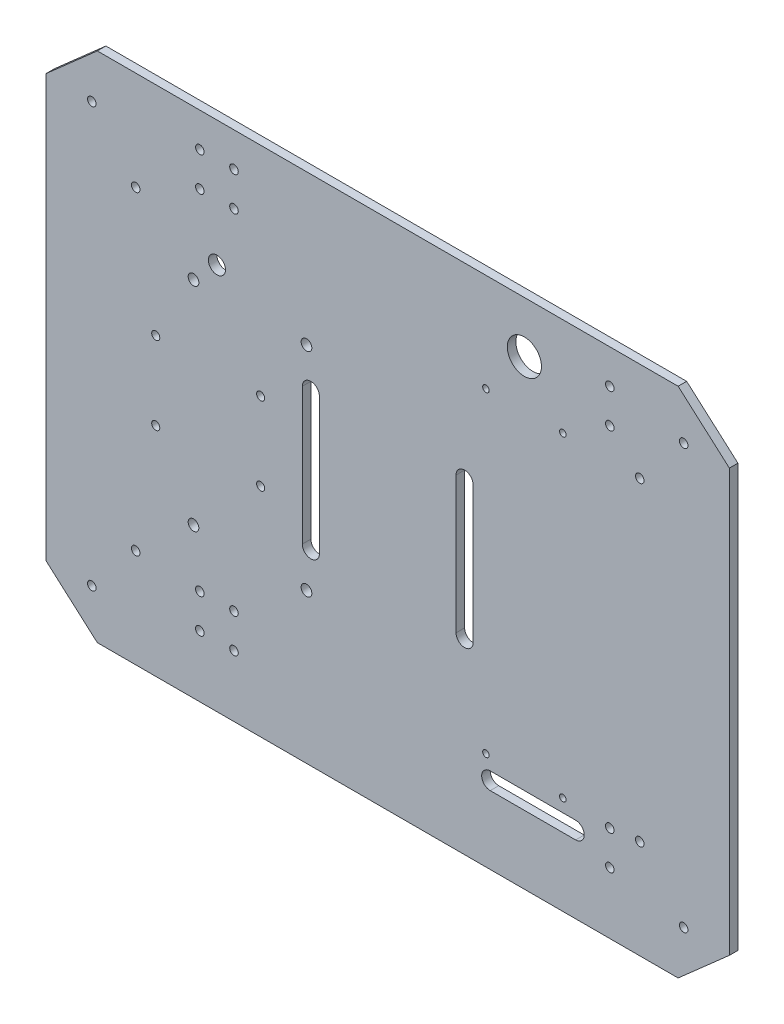
SolidWorks part; units mm, degrees
material "Thornel Mat VMA"
ref_plane "Front Plane" through (0, 0, 0) normal (0, 0, 1) x (1, 0, 0)
ref_plane "Top Plane" through (0, 0, 0) normal (0, 1, 0) x (1, 0, 0)
ref_plane "Right Plane" through (0, 0, 0) normal (1, 0, 0) x (0, 0, -1)
sketch "Sketch1" plane through (0, 0, 0) normal (0, 0, 1) x (1, 0, 0)
  line L0 (-127, 0) -> (127, 0) construction
  line L1 (0, -95.25) -> (0, 95.25) construction
  line L2 (-107.95, 0) -> (-107.95, 40.5993) construction
  line L3 (-107.95, 40.5993) -> (-95.25, 40.5993) construction
  line L4 (-95.25, 40.5993) -> (-75.7925, 56.9261) construction
  line L5 (-75.7925, 56.9261) -> (-75.7925, 76.2) construction
  line L6 (-75.7925, 76.2) -> (0, 76.2) construction
  line L7 (-95.25, 40.5993) -> (-127, 78.4375) construction
  line L8 (-75.7925, 56.9261) -> (-107.95, 95.25) construction
  line L24 (127, -78.4375) -> (127, 78.4375)
  line L25 (127, 78.4375) -> (107.95, 95.25)
  line L26 (107.95, 95.25) -> (-107.95, 95.25)
  line L27 (-107.95, 95.25) -> (-127, 78.4375)
  line L28 (-127, 78.4375) -> (-127, -78.4375)
  line L29 (-127, -78.4375) -> (-107.95, -95.25)
  line L30 (-107.95, -95.25) -> (107.95, -95.25)
  line L31 (107.95, -95.25) -> (127, -78.4375)
  point P12 (0, 0)
  dimension "D1" = 190.5
  dimension "D2" = 254
  dimension "D3" = 19.05
  dimension "D4" = 19.05
  dimension "D5" = 12.7
  dimension "D6" = 25.4
  dimension "D7" = 40
extrude "Boss-Extrude1" add sketch "Sketch1" along normal blind 3.175
sketch "Sketch2" plane through (0, 0, 3.175) normal (0, 0, 1) x (1, 0, 0)
  line L0 (-127, 0) -> (127, 0) construction
  line L1 (-127, 78.4375) -> (-127, -78.4375) construction
  line L2 (127, -78.4375) -> (127, 78.4375) construction
  line L3 (50.8, 65.0875) -> (50.8, -65.0875) construction
  line L4 (31.75, 65.0875) -> (69.85, 65.0875)
  line L5 (31.75, 65.0875) -> (31.75, -65.0875)
  line L6 (31.75, -65.0875) -> (69.85, -65.0875)
  line L7 (69.85, 65.0875) -> (69.85, -65.0875)
  line L8 (31.75, 65.0875) -> (69.85, -65.0875) construction
  line L9 (31.75, -65.0875) -> (69.85, 65.0875) construction
  line L10 (50.8, 58.7375) -> (41.275, 58.7375) construction
  line L11 (41.275, 58.7375) -> (31.75, 58.7375) construction
  circle A0 centre (36.5125, 58.7375) radius 1.2136
  circle A1 centre (36.5125, -58.7375) radius 1.2136
  circle A2 centre (65.0875, -58.7375) radius 1.2136
  circle A3 centre (65.0875, 58.7375) radius 1.2136
  point P6 (50.8, 0)
  point P17 (36.5125, 58.7375)
  dimension "D1" = 38.1
  dimension "D2" = 130.175
  dimension "D3" = 6.35
  dimension "D4" = 9.525
  dimension "D5" = 76.2
extrude "Cut-Extrude1" cut sketch "Sketch2" against normal through all contours A1 | A2 | A3 | A0 region at (36.5125, 58.7375, 3.175) region at (36.5125, -58.7375, 3.175) region at (65.0875, -58.7375, 3.175) region at (65.0875, 58.7375, 3.175)
sketch "Sketch3" plane through (0, 0, 3.175) normal (0, 0, 1) x (1, 0, 0)
  line L0 (0, 95.25) -> (0, -95.25) construction
  line L1 (107.95, 95.25) -> (-107.95, 95.25) construction
  line L2 (-107.95, -95.25) -> (107.95, -95.25) construction
  line L3 (127, 0) -> (-127, 0) construction
  line L4 (127, -78.4375) -> (127, 78.4375) construction
  line L5 (-127, 78.4375) -> (-127, -78.4375) construction
  line L6 (127, -78.4375) -> (127, -95.25) construction
  line L7 (127, -95.25) -> (107.95, -95.25) construction
  line L8 (127, -95.25) -> (162.6067, -130.8567) construction
  circle A0 centre (162.6067, -130.8567) radius 1.9844
  circle A1 centre (180.5672, -148.8172) radius 1.9844
  dimension "D2" = 3.9688
  dimension "D3" = 3.9688
  dimension "D1" = 45
  dimension "D4" = 25.4
sketch "Sketch5" plane through (0, 0, 0) normal (0, 0, -1) x (-1, 0, 0)
  line L0 (-127, 0) -> (127, 0) construction
  line L1 (76.2, 43.5) -> (26.2001, 43.5)
  line L2 (76.2, 43.5) -> (76.2, -43.5)
  line L3 (76.2, -43.5) -> (26.2001, -43.5)
  line L4 (26.2001, 43.5) -> (26.2001, -43.5)
  line L5 (76.2, 43.5) -> (26.2001, -43.5) construction
  line L6 (76.2, -43.5) -> (26.2001, 43.5) construction
  line L7 (127, 78.4375) -> (127, -78.4375) construction
  line L8 (0, 64.0679) -> (0, -49.8393) construction
  line L9 (-76.2, 47.625) -> (-31.75, 47.625)
  line L10 (-76.2, 47.625) -> (-76.2, -47.625)
  line L11 (-76.2, -47.625) -> (-31.75, -47.625)
  line L12 (-31.75, 47.625) -> (-31.75, -47.625)
  line L13 (-76.2, 47.625) -> (-31.75, -47.625) construction
  line L14 (-76.2, -47.625) -> (-31.75, 47.625) construction
  line L15 (-69.85, -66.675) -> (-38.1, -66.675) construction
  line L16 (-69.85, -63.5) -> (-38.1, -63.5)
  line L17 (-69.85, -69.85) -> (-38.1, -69.85)
  line L18 (107.95, -95.25) -> (-107.95, -95.25) construction
  line L19 (-28.575, 25.4) -> (-28.575, -25.4) construction
  line L20 (-107.95, 95.25) -> (107.95, 95.25) construction
  line L21 (-127, -78.4375) -> (-127, 78.4375) construction
  line L22 (-50.8, 76.2) -> (63.5, 76.2) construction
  line L23 (63.5, 76.2) -> (63.5, 48.58) construction
  line L24 (-53.975, -66.675) -> (63.5, -66.675) construction
  line L25 (63.5, -66.675) -> (63.5, 48.58) construction
  line L26 (127, 0) -> (-127, 0) construction
  line L27 (51.2, 0) -> (51.2, -8419.0368) construction
  line L28 (-25.4, 25.4) -> (-25.4, -25.4)
  line L29 (-31.75, 25.4) -> (-31.75, -25.4)
  line L30 (28.575, 25.4) -> (28.575, -25.4) construction
  line L31 (25.4, 25.4) -> (25.4, -25.4)
  line L32 (31.75, 25.4) -> (31.75, -25.4)
  line L33 (66.7369, 0) -> (66.7369, 12.9123) construction
  line L34 (44.2369, 17.5) -> (89.2369, 17.5)
  line L35 (44.2369, 17.5) -> (44.2369, -17.5)
  line L36 (44.2369, -17.5) -> (89.2369, -17.5)
  line L37 (89.2369, 17.5) -> (89.2369, -17.5)
  line L38 (44.2369, 17.5) -> (89.2369, -17.5) construction
  line L39 (44.2369, -17.5) -> (89.2369, 17.5) construction
  arc A0 (-69.85, -63.5) -> (-69.85, -69.85) centre (-69.85, -66.675) ccw
  arc A1 (-38.1, -69.85) -> (-38.1, -63.5) centre (-38.1, -66.675) ccw
  circle A2 centre (63.5, 48.58) radius 3.175
  circle A3 centre (-50.8, 76.2) radius 6.35
  circle A4 centre (57.15, 69.85) radius 1.5875
  circle A5 centre (57.15, 82.55) radius 1.5875
  circle A6 centre (57.15, -72.39) radius 1.5875
  circle A7 centre (57.15, -59.69) radius 1.5875
  circle A8 centre (69.85, -72.39) radius 1.5875
  circle A9 centre (69.85, -59.69) radius 1.5875
  circle A10 centre (69.85, 82.55) radius 1.5875
  circle A11 centre (69.85, 69.85) radius 1.5875
  circle A12 centre (30.2006, 39.4995) radius 1.9844
  circle A13 centre (72.1995, 39.4995) radius 1.9844
  circle A14 centre (30.2006, -39.4995) radius 1.9844
  circle A15 centre (72.1995, -39.4995) radius 1.9844
  circle A16 centre (-82.55, -59.69) radius 1.5875
  circle A17 centre (-82.55, -72.39) radius 1.5875
  circle A18 centre (-82.55, 82.55) radius 1.5875
  circle A19 centre (-82.55, 69.85) radius 1.5875
  arc A20 (-25.4, 25.4) -> (-31.75, 25.4) centre (-28.575, 25.4) ccw
  arc A21 (-31.75, -25.4) -> (-25.4, -25.4) centre (-28.575, -25.4) ccw
  arc A22 (25.4, 25.4) -> (31.75, 25.4) centre (28.575, 25.4) cw
  arc A23 (31.75, -25.4) -> (25.4, -25.4) centre (28.575, -25.4) cw
  circle A24 centre (47.2369, 14.5) radius 1.5
  circle A25 centre (47.2369, -14.5) radius 1.5
  circle A26 centre (86.2369, -14.5) radius 1.5
  circle A27 centre (86.2369, 14.5) radius 1.5
  point P0 (51.2, 0)
  point P9 (-53.975, 0)
  point P18 (-53.975, -66.675)
  point P77 (-28.575, 0)
  point P84 (28.575, 0)
  point P89 (66.7369, 0)
  dimension "D10" = 6.35
  dimension "D15" = 12.7
  dimension "D17" = 3.175
  dimension "D18" = 3.175
  dimension "D21" = 3.175
  dimension "D22" = 3.175
  dimension "D25" = 4.0005
  dimension "D27" = 3.9688
  dimension "D28" = 3.175
  dimension "D29" = 3.175
  dimension "D30" = 12.7
  dimension "D33" = 3.175
  dimension "D34" = 3.175
  dimension "D45" = 3
  dimension "D1" = 87.0001
  dimension "D2" = 49.9999
  dimension "D3" = 50.8
  dimension "D4" = 95.25
  dimension "D5" = 44.45
  dimension "D6" = 50.8
  dimension "D7" = 31.75
  dimension "D8" = 6.35
  dimension "D9" = 28.575
  dimension "D11" = 5.08
  dimension "D12" = 12.7
  dimension "D13" = 19.05
  dimension "D14" = 76.2
  dimension "D16" = 12.7
  dimension "D19" = 6.35
  dimension "D20" = 12.7
  dimension "D23" = 12.7
  dimension "D24" = 22.86
  dimension "D26" = 4.0005
  dimension "D31" = 5.715
  dimension "D32" = 44.45
  dimension "D35" = 12.7
  dimension "D36" = 6.35
  dimension "D37" = 44.45
  dimension "D38" = 50.8
  dimension "D39" = 6.35
  dimension "D40" = 28.575
  dimension "D41" = 45
  dimension "D42" = 35
  dimension "D43" = 3
  dimension "D44" = 3
extrude "Cut-Extrude2" cut sketch "Sketch5" against normal through all contours A3 | L17 A1 L16 A0 | A2 | A5 | A4 | A6 | A7 | A8 | A9 | A10 | A11 | A14 | A15 | A13 | A12 | A19 | A18 | A17 | A16 | L29 A21 L28 A20 | A23 L4 A22 L31 | A23 L32 A22 L4 | A27 | A24 | A25 | A26 | A4 | A19 region at (-28.9574, 0, 0) region at (-25.8042, 0, 0) region at (28.575, 0, 0) region at (53.975, -66.675, 0) region at (-63.5, 48.58, 0) region at (50.8, 76.2, 0) region at (-57.15, 69.85, 0) region at (-57.15, 82.55, 0) region at (-57.15, -72.39, 0) region at (-57.15, -59.69, 0) region at (-69.85, -72.39, 0) region at (-69.85, -59.69, 0) region at (-69.85, 82.55, 0) region at (-69.85, 69.85, 0) region at (-30.2006, 39.4995, 0) region at (-72.1995, 39.4995, 0) region at (-30.2006, -39.4995, 0) region at (-72.1995, -39.4995, 0) region at (82.55, -59.69, 0) region at (82.55, -72.39, 0) region at (82.55, 82.55, 0) region at (82.55, 69.85, 0) region at (-47.2369, 14.5, 0) region at (-47.2369, -14.5, 0) region at (-86.2369, -14.5, 0) region at (-86.2369, 14.5, 0)
sketch "Sketch7" plane through (0, 0, 3.175) normal (0, 0, 1) x (1, 0, 0)
  line L0 (-85.5212, 48.7627) -> (-110.0114, 77.949) construction
  line L1 (-95.25, 40.5993) -> (-75.7925, 56.9261) construction
  line L2 (0, 0) -> (0, 136.2248) construction
  line L3 (0, 0) -> (-169.7597, 0) construction
  circle A0 centre (-110.0114, 77.949) radius 1.5875
  circle A1 centre (-93.6846, 58.4915) radius 1.5875
  circle A2 centre (110.0114, 77.949) radius 1.5875
  circle A3 centre (93.6846, 58.4915) radius 1.5875
  circle A4 centre (110.0114, -77.949) radius 1.5875
  circle A5 centre (93.6846, -58.4915) radius 1.5875
  circle A6 centre (-110.0114, -77.949) radius 1.5875
  circle A7 centre (-93.6846, -58.4915) radius 1.5875
  dimension "D2" = 3.175
  dimension "D3" = 3.175
  dimension "D1" = 25.4
  dimension "D4" = 12.7
extrude "Cut-Extrude3" cut sketch "Sketch7" against normal through all
